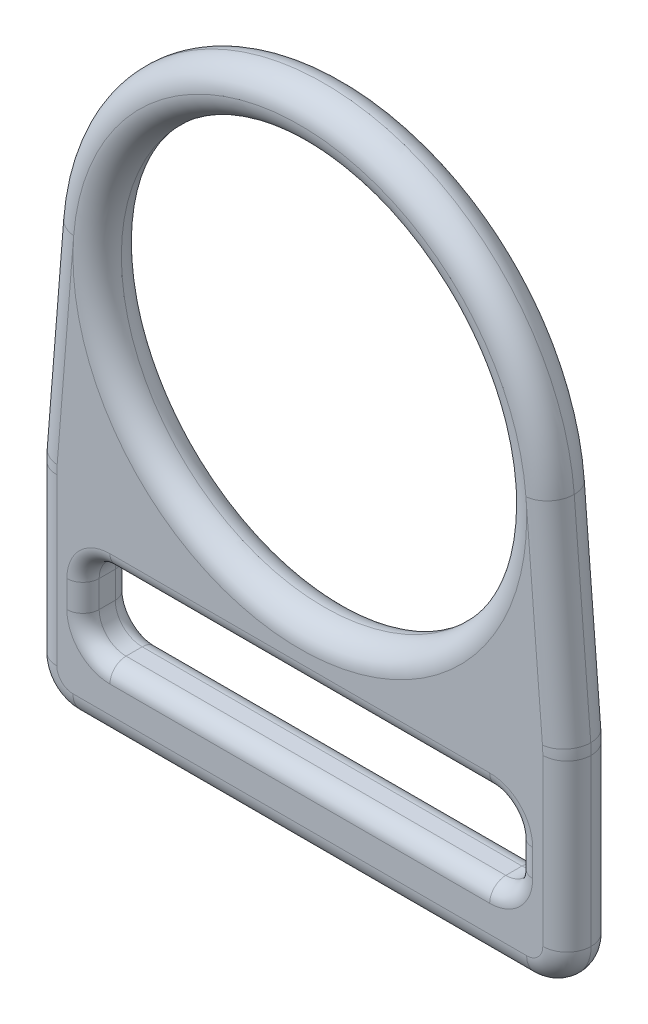
SolidWorks part; units mm, degrees
ref_plane "Front Plane" through (0, 0, 0) normal (0, 0, 1) x (1, 0, 0)
ref_plane "Top Plane" through (0, 0, 0) normal (0, 1, 0) x (1, 0, 0)
ref_plane "Right Plane" through (0, 0, 0) normal (1, 0, 0) x (0, 0, -1)
sketch "Sketch2" plane through (0, 0, 0) normal (1, 0, 0) x (0, 0, -1)
  circle A0 centre (0, 0) radius 2.286
  dimension "D1" = 4.572
sketch "Sketch3" plane through (0, 0, 0) normal (0, 0, 1) x (1, 0, 0)
  circle A0 centre (0, -21.4312) radius 21.4312
  dimension "D1" = 42.8625
sweep "Sweep1" add profiles "Sketch2" path "Sketch3"
sketch "Sketch4" plane through (0, 0, 0) normal (0, 0, 1) x (1, 0, 0)
  line L0 (-23.6421, -19.5444) -> (-25.201, -39.078)
  line L1 (-25.2412, -40.0883) -> (-25.2412, -55.7213)
  line L2 (-21.4312, -59.5312) -> (21.4312, -59.5312)
  line L3 (25.2412, -55.7213) -> (25.2412, -40.0883)
  line L4 (25.201, -39.078) -> (23.6421, -19.5444)
  line L5 (-20.4788, -48.1013) -> (-20.4788, -50.6412)
  line L6 (-17.9387, -53.1812) -> (17.9387, -53.1812)
  line L7 (20.4788, -50.6412) -> (20.4788, -48.1013)
  line L8 (17.9387, -45.5613) -> (-17.9387, -45.5613)
  line L9 (0, -21.4312) -> (0, -59.5312) construction
  arc A2 (21.4312, -59.5312) -> (25.2412, -55.7213) centre (21.4312, -55.7213) ccw
  arc A3 (-25.2412, -55.7213) -> (-21.4312, -59.5312) centre (-21.4312, -55.7213) ccw
  arc A4 (20.4788, -48.1013) -> (17.9387, -45.5613) centre (17.9387, -48.1013) ccw
  arc A5 (17.9387, -53.1812) -> (20.4788, -50.6412) centre (17.9387, -50.6412) ccw
  arc A6 (-20.4788, -50.6412) -> (-17.9387, -53.1812) centre (-17.9387, -50.6412) ccw
  arc A7 (-20.4788, -48.1013) -> (-17.9387, -45.5613) centre (-17.9387, -48.1013) cw
  arc A8 (25.2412, -40.0883) -> (25.201, -39.078) centre (12.5412, -40.0883) ccw
  arc A9 (-25.201, -39.078) -> (-25.2412, -40.0883) centre (-12.5412, -40.0883) ccw
  circle A10 centre (0, -21.4312) radius 23.7172 construction
  arc A11 (23.6421, -19.5444) -> (-23.6421, -19.5444) centre (0, -21.4312) ccw
  circle A12 centre (0, -21.4312) radius 19.1453 construction
  circle A13 centre (0, -21.4312) radius 19.1453
  point P30 (0, 2.286)
  dimension "D1" = 3.81
  dimension "D2" = 2.54
  dimension "D3" = 12.7
  dimension "D4" = 6.35
  dimension "D5" = 4.7625
  dimension "D6" = 42.8625
  dimension "D7" = 7.62
  dimension "D8" = 38.1
  dimension "D9" = 19.5335
extrude "Boss-Extrude1" add sketch "Sketch4" along normal through all and the other way through all
fillet "Fillet1" radius 2.286 22 edges at (24.4215, -29.3112, 2.286) (25.2312, -39.5827, 2.286) (25.2413, -47.9048, 2.286) (24.1253, -58.4153, 2.286) (0, -59.5312, 2.286) (-24.1253, -58.4153, 2.286) (-25.2412, -47.9048, 2.286) (-25.2312, -39.5827, 2.286) (-24.4215, -29.3112, 2.286) (24.4215, -29.3112, -2.286) (25.2312, -39.5827, -2.286) (25.2413, -47.9048, -2.286) (24.1253, -58.4153, -2.286) (0, -59.5312, -2.286) (-24.1253, -58.4153, -2.286) (-25.2412, -47.9048, -2.286) (-25.2312, -39.5827, -2.286) (-24.4215, -29.3112, -2.286) (19.1453, -21.4312, 2.286) (19.1453, -21.4312, -2.286) (0, 2.286, 2.286) (0, 2.286, -2.286)
fillet "Fillet2" radius 1.524 16 edges at (-19.7348, -52.4373, 2.286) (-20.4787, -49.3713, 2.286) (-19.7348, -46.3052, 2.286) (0, -45.5613, 2.286) (19.7348, -46.3052, 2.286) (20.4788, -49.3713, 2.286) (19.7348, -52.4373, 2.286) (-19.7348, -52.4373, -2.286) (-20.4787, -49.3713, -2.286) (-19.7348, -46.3052, -2.286) (0, -45.5613, -2.286) (19.7348, -46.3052, -2.286) (20.4788, -49.3713, -2.286) (19.7348, -52.4373, -2.286) (0, -53.1812, 2.286) (0, -53.1812, -2.286)
